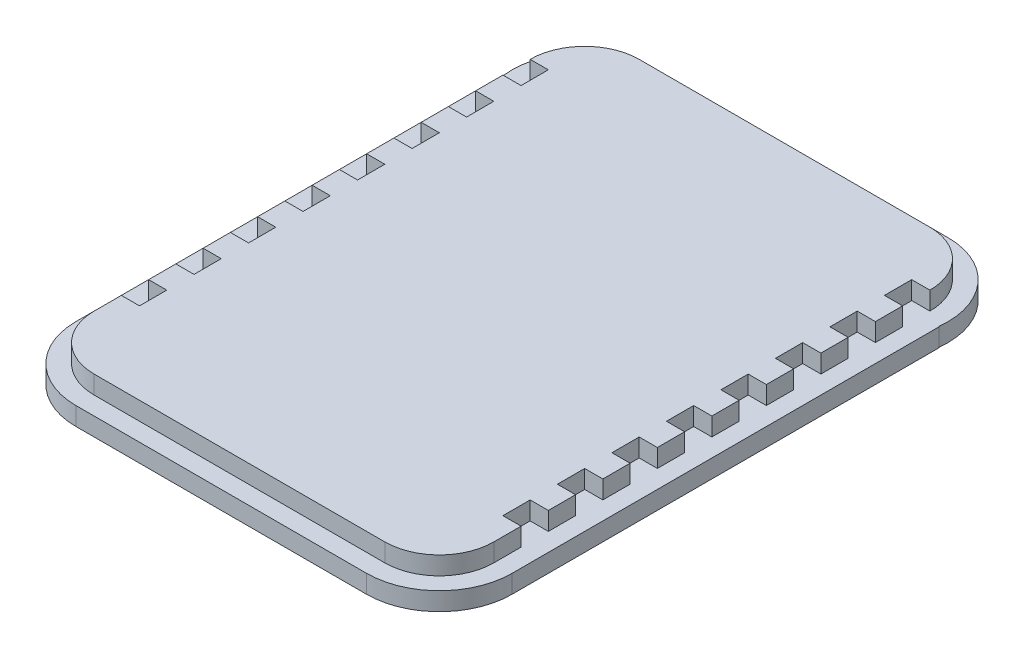
SolidWorks part; units mm, degrees
ref_plane "Front Plane" through (0, 0, 0) normal (0, 0, 1) x (1, 0, 0)
ref_plane "Top Plane" through (0, 0, 0) normal (0, 1, 0) x (1, 0, 0)
ref_plane "Right Plane" through (0, 0, 0) normal (1, 0, 0) x (0, 0, -1)
sketch "Sketch1" plane through (0, 0, 0) normal (0, 1, 0) x (1, 0, 0)
  line L0 (144.3558, 286.3848) -> (805.6847, 286.3848) construction
  line L2 (0, 0) -> (220, 0)
  line L3 (0, 0) -> (0, 300)
  line L4 (0, 300) -> (220, 300)
  line L5 (220, 0) -> (220, 300)
  dimension "D1" = 220
  dimension "D2" = 300
extrude "Boss-Extrude1" add sketch "Sketch1" along normal blind 10
fillet "Fillet1" radius 30 4 edges at (0, 5, 0) (220, 5, 0) (220, 5, -300) (0, 5, -300)
sketch "Sketch8" plane through (0, 0, 0) normal (-1, 0, 0) x (0, 0, 1)
  line L0 (-270, 0) -> (-30, 0) construction
  line L1 (-270, 0) -> (-255, 0)
  line L2 (-270, 0) -> (-270, 10)
  line L3 (-270, 10) -> (-255, 10)
  line L4 (-255, 0) -> (-255, 10)
  line L5 (-270, 10) -> (-270, 0) construction
  line L6 (-270, 10) -> (-30, 10) construction
  line L7 (-255, 0) -> (-255, 10)
  line L8 (-255, 0) -> (-240, 0)
  line L9 (-240, 0) -> (-240, 10)
  line L10 (-255, 10) -> (-240, 10)
  line L11 (-240, 0) -> (-240, 10)
  line L12 (-240, 0) -> (-225, 0)
  line L13 (-225, 0) -> (-225, 10)
  line L14 (-240, 10) -> (-225, 10)
  line L15 (-225, 0) -> (-225, 10)
  line L16 (-225, 0) -> (-210, 0)
  line L17 (-210, 0) -> (-210, 10)
  line L18 (-225, 10) -> (-210, 10)
  line L19 (-210, 0) -> (-210, 10)
  line L20 (-210, 0) -> (-195, 0)
  line L21 (-195, 0) -> (-195, 10)
  line L22 (-210, 10) -> (-195, 10)
  line L23 (-195, 0) -> (-195, 10)
  line L24 (-195, 0) -> (-180, 0)
  line L25 (-180, 0) -> (-180, 10)
  line L26 (-195, 10) -> (-180, 10)
  line L27 (-180, 0) -> (-180, 10)
  line L28 (-180, 0) -> (-165, 0)
  line L29 (-165, 0) -> (-165, 10)
  line L30 (-180, 10) -> (-165, 10)
  line L31 (-165, 0) -> (-165, 10)
  line L32 (-165, 0) -> (-150, 0)
  line L33 (-150, 0) -> (-150, 10)
  line L34 (-165, 10) -> (-150, 10)
  line L35 (-150, 0) -> (-150, 10)
  line L36 (-150, 0) -> (-135, 0)
  line L37 (-135, 0) -> (-135, 10)
  line L38 (-150, 10) -> (-135, 10)
  line L39 (-135, 0) -> (-135, 10)
  line L40 (-135, 0) -> (-120, 0)
  line L41 (-120, 0) -> (-120, 10)
  line L42 (-135, 10) -> (-120, 10)
  line L43 (-120, 0) -> (-120, 10)
  line L44 (-120, 0) -> (-105, 0)
  line L45 (-105, 0) -> (-105, 10)
  line L46 (-120, 10) -> (-105, 10)
  line L47 (-105, 0) -> (-105, 10)
  line L48 (-105, 0) -> (-90, 0)
  line L49 (-90, 0) -> (-90, 10)
  line L50 (-105, 10) -> (-90, 10)
  line L51 (-90, 0) -> (-90, 10)
  line L52 (-90, 0) -> (-75, 0)
  line L53 (-75, 0) -> (-75, 10)
  line L54 (-90, 10) -> (-75, 10)
  line L55 (-75, 0) -> (-75, 10)
  line L56 (-75, 0) -> (-60, 0)
  line L57 (-60, 0) -> (-60, 10)
  line L58 (-75, 10) -> (-60, 10)
  line L59 (-60, 0) -> (-60, 10)
  line L60 (-60, 0) -> (-45, 0)
  line L61 (-45, 0) -> (-45, 10)
  line L62 (-60, 10) -> (-45, 10)
  line L63 (-45, 0) -> (-45, 10)
  line L64 (-45, 0) -> (-30, 0)
  line L65 (-30, 0) -> (-30, 10)
  line L66 (-45, 10) -> (-30, 10)
  line M5 (-270, 0) -> (-30, 0)
  line M7 (-30, 10) -> (-270, 10)
  line M8 (-270, 10) -> (-270, 0)
  dimension "D1" = 15
  dimension "D2" = 16
sketch "Sketch9" plane through (220, 0, 0) normal (1, 0, 0) x (0, 0, -1)
  line L0 (30, 0) -> (270, 0) construction
  line L1 (30, 10) -> (45, 10)
  line L2 (30, 10) -> (30, 0)
  line L3 (30, 0) -> (45, 0)
  line L4 (45, 10) -> (45, 0)
  line L5 (45, 10) -> (45, 0)
  line L6 (45, 10) -> (60, 10)
  line L7 (60, 10) -> (60, 0)
  line L8 (45, 0) -> (60, 0)
  line L9 (60, 10) -> (60, 0)
  line L10 (60, 10) -> (75, 10)
  line L11 (75, 10) -> (75, 0)
  line L12 (60, 0) -> (75, 0)
  line L13 (75, 10) -> (75, 0)
  line L14 (75, 10) -> (90, 10)
  line L15 (90, 10) -> (90, 0)
  line L16 (75, 0) -> (90, 0)
  line L17 (90, 10) -> (90, 0)
  line L18 (90, 10) -> (105, 10)
  line L19 (105, 10) -> (105, 0)
  line L20 (90, 0) -> (105, 0)
  line L21 (105, 10) -> (105, 0)
  line L22 (105, 10) -> (120, 10)
  line L23 (120, 10) -> (120, 0)
  line L24 (105, 0) -> (120, 0)
  line L25 (120, 10) -> (120, 0)
  line L26 (120, 10) -> (135, 10)
  line L27 (135, 10) -> (135, 0)
  line L28 (120, 0) -> (135, 0)
  line L29 (135, 10) -> (135, 0)
  line L30 (135, 10) -> (150, 10)
  line L31 (150, 10) -> (150, 0)
  line L32 (135, 0) -> (150, 0)
  line L33 (150, 10) -> (150, 0)
  line L34 (150, 10) -> (165, 10)
  line L35 (165, 10) -> (165, 0)
  line L36 (150, 0) -> (165, 0)
  line L37 (165, 10) -> (165, 0)
  line L38 (165, 10) -> (180, 10)
  line L39 (180, 10) -> (180, 0)
  line L40 (165, 0) -> (180, 0)
  line L41 (180, 10) -> (180, 0)
  line L42 (180, 10) -> (195, 10)
  line L43 (195, 10) -> (195, 0)
  line L44 (180, 0) -> (195, 0)
  line L45 (195, 10) -> (195, 0)
  line L46 (195, 10) -> (210, 10)
  line L47 (210, 10) -> (210, 0)
  line L48 (195, 0) -> (210, 0)
  line L49 (210, 10) -> (210, 0)
  line L50 (210, 10) -> (225, 10)
  line L51 (225, 10) -> (225, 0)
  line L52 (210, 0) -> (225, 0)
  line L53 (225, 10) -> (225, 0)
  line L54 (225, 10) -> (240, 10)
  line L55 (240, 10) -> (240, 0)
  line L56 (225, 0) -> (240, 0)
  line L57 (240, 10) -> (240, 0)
  line L58 (240, 10) -> (255, 10)
  line L59 (255, 10) -> (255, 0)
  line L60 (240, 0) -> (255, 0)
  line L61 (255, 10) -> (255, 0)
  line L62 (255, 10) -> (270, 10)
  line L63 (270, 10) -> (270, 0)
  line L64 (255, 0) -> (270, 0)
  line L65 (30, 10) -> (45, 10) construction
  line M9 (270, 10) -> (30, 10)
  line M11 (30, 0) -> (270, 0)
  line M12 (270, 0) -> (270, 10)
  dimension "D1" = 15
  dimension "D3" = 15
  dimension "D2" = 16
extrude "Cut-Extrude1" cut sketch "Sketch9" against normal blind 10 contours L59 M9 M11 M12 | L55 L51 M9 M11 | L47 L43 M9 M11 | L39 L35 M9 M11 | L31 L27 M9 M11 | L23 L19 M9 M11 | L15 L11 M9 M11 | L7 L4 M9 M11 region at (220, 5, -52.5) region at (220, 5, -82.5) region at (220, 5, -112.5) region at (220, 5, -142.5) region at (220, 5, -172.5) region at (220, 5, -202.5) region at (220, 5, -232.5) region at (220, 5, -262.5)
extrude "Cut-Extrude2" cut sketch "Sketch8" against normal blind 10 contours L4 M5 M7 M8 | L13 L9 M5 M7 | L21 L17 M5 M7 | L29 L25 M5 M7 | L37 L33 M5 M7 | L45 L41 M5 M7 | L53 L49 M5 M7 | L61 L57 M5 M7 region at (0, 5, -262.5) region at (0, 5, -232.5) region at (0, 5, -202.5) region at (0, 5, -172.5) region at (0, 5, -142.5) region at (0, 5, -112.5) region at (0, 5, -82.5) region at (0, 5, -52.5)
sketch "Sketch11" plane through (0, 0, 0) normal (0, -1, 0) x (1, 0, 0)
  line L132 (30, -310) -> (190, -310)
  line L133 (229.6863, -265) -> (230, -265)
  line L134 (230, -265) -> (230, -30)
  line L135 (190, 10) -> (30, 10)
  line L136 (-10, -30) -> (-10, -265)
  line L137 (-10, -265) -> (-9.6863, -265)
  line L138 (30, -310) -> (190, -310)
  line L139 (229.6863, -265) -> (230, -265)
  line L140 (230, -265) -> (230, -30)
  line L141 (190, 10) -> (30, 10)
  line L142 (-10, -30) -> (-10, -265)
  line L143 (-10, -265) -> (-9.6863, -265)
  arc A8 (-9.6863, -265) -> (30, -310) centre (30, -270) ccw
  arc A9 (190, -310) -> (229.6863, -265) centre (190, -270) ccw
  arc A10 (230, -30) -> (190, 10) centre (190, -30) ccw
  arc A11 (30, 10) -> (-10, -30) centre (30, -30) ccw
  arc A12 (-9.6863, -265) -> (30, -310) centre (30, -270) ccw
  arc A13 (190, -310) -> (229.6863, -265) centre (190, -270) ccw
  arc A14 (230, -30) -> (190, 10) centre (190, -30) ccw
  arc A15 (30, 10) -> (-10, -30) centre (30, -30) ccw
  dimension "D1" = 10
extrude "Boss-Extrude3" add sketch "Sketch11" along normal blind 10
